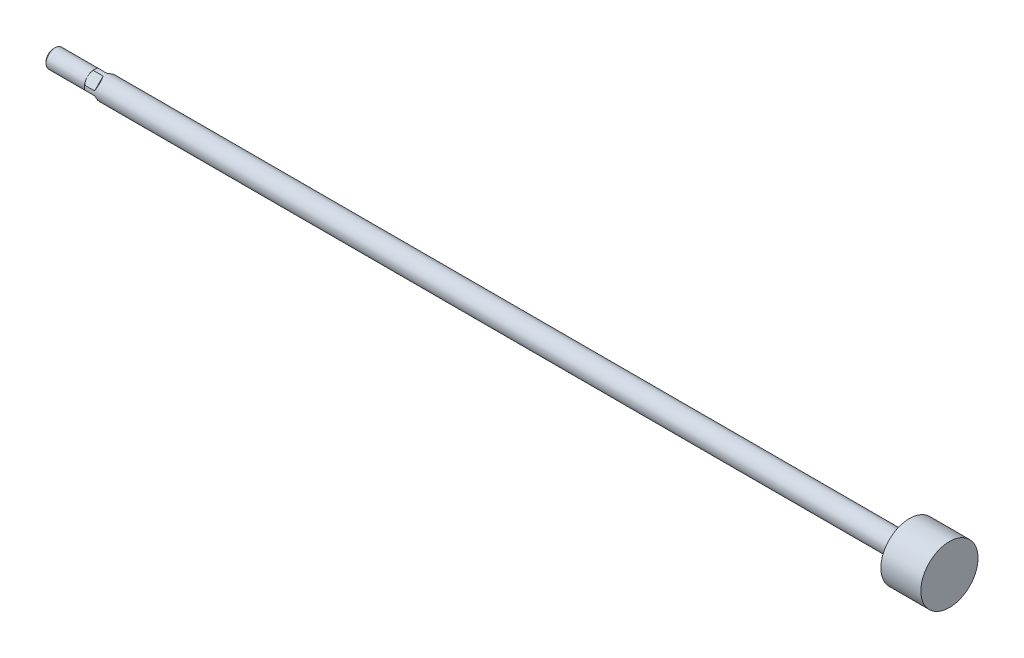
SolidWorks part; units mm, degrees
ref_plane "前视基准面" through (0, 0, 0) normal (0, 0, 1) x (1, 0, 0)
ref_plane "上视基准面" through (0, 0, 0) normal (0, 1, 0) x (1, 0, 0)
ref_plane "右视基准面" through (0, 0, 0) normal (1, 0, 0) x (0, 0, -1)
sketch "草图1" plane through (0, 0, 0) normal (0, 0, 1) x (1, 0, 0)
  line L0 (0, 0) -> (0, 4.233)
  line L1 (0, 4.233) -> (0.767, 5)
  line L2 (0.767, 5) -> (22, 5)
  line L3 (22, 5) -> (23, 6)
  line L4 (23, 6) -> (471, 6)
  line L5 (471, 6) -> (471, 15.75)
  line L6 (471, 15.75) -> (493, 15.75)
  line L7 (493, 15.75) -> (493, 0)
  line L8 (493, 0) -> (0, 0)
  line L9 (493, 0) -> (0, 0) construction
revolve "旋转1" add sketch "草图1" angle 360 about L9 reverse direction yes
cosmetic thread "装饰螺纹线1" parameters "D1"=22, "D2"=8.466
ref_plane "基准面4" through (30, 0, 0) normal (1, 0, 0) x (0, 0, -1)
ref_plane "基准面5" through (11, 0, 0) normal (1, 0, 0) x (0, 0, -1)
ref_plane "基准面6" through (0, 0, 0) normal (0, -0.7071, 0.7071) x (1, 0, 0)
sketch "草图2" plane through (0, 0, 0) normal (0, -0.7071, 0.7071) x (1, 0, 0)
  line L0 (-5, -12) -> (35.4, -12)
  line L1 (35.4, -12) -> (28.4, -5)
  line L2 (28.4, -5) -> (22, -5)
  line L3 (22, -5) -> (19.8, -7.2)
  line L4 (19.8, -7.2) -> (19.8, -10)
  line L5 (19.8, -10) -> (-3, -10)
  line L6 (-3, -10) -> (-3, 10)
  line L7 (-3, 10) -> (19.8, 10)
  line L8 (19.8, 10) -> (19.8, 7.2)
  line L9 (19.8, 7.2) -> (22, 5)
  line L10 (22, 5) -> (28.4, 5)
  line L11 (28.4, 5) -> (35.4, 12)
  line L12 (35.4, 12) -> (-5, 12)
  line L13 (-5, 12) -> (-5, -12)
extrude "切除-拉伸1" cut sketch "草图2" along normal blind 5 and the other way blind 5
ref_plane "基准面7" through (0, 0, 0) normal (0, -0.7071, -0.7071) x (-1, 0, 0)
sketch "草图3" plane through (0, 0, 0) normal (0, -0.7071, -0.7071) x (-1, 0, 0)
  line L0 (5, 12) -> (-35.4, 12)
  line L1 (-35.4, 12) -> (-28.4, 5)
  line L2 (-28.4, 5) -> (-22, 5)
  line L3 (-22, 5) -> (-19.8, 7.2)
  line L4 (-19.8, 7.2) -> (-19.8, 10)
  line L5 (-19.8, 10) -> (3, 10)
  line L6 (3, 10) -> (3, -10)
  line L7 (3, -10) -> (-19.8, -10)
  line L8 (-19.8, -10) -> (-19.8, -7.2)
  line L9 (-19.8, -7.2) -> (-22, -5)
  line L10 (-22, -5) -> (-28.4, -5)
  line L11 (-28.4, -5) -> (-35.4, -12)
  line L12 (-35.4, -12) -> (5, -12)
  line L13 (5, -12) -> (5, 12)
extrude "切除-拉伸2" cut sketch "草图3" along normal blind 5 and the other way blind 5
ref_plane "nut-rod XY" through (11, 0, 0) normal (-1, 0, 0) x (0, 0, 1)
ref_plane "nut-rod XZ" through (0, 0, 0) normal (0, 1, 0) x (1, 0, 0)
ref_plane "nut-rod YZ" through (0, 0, 0) normal (0, 0, -1) x (-1, 0, 0)
ref_axis "nut-rod X" through (11, 0, 80.9) along (0, 0, -1)
ref_axis "nut-rod Y" through (11, 50, 0) along (0, -1, 0)
ref_axis "nut-rod Z" through (-80.9, 0, 0) along (1, 0, 0)
sketch3d "nut-rod"
  point P0 (11, 0, 0)
ref_plane "rod XY" through (30, 0, 0) normal (-1, 0, 0) x (0, 0, 1)
ref_plane "rod XZ" through (0, 0, 0) normal (0, 1, 0) x (1, 0, 0)
ref_plane "rod YZ" through (0, 0, 0) normal (0, 0, -1) x (-1, 0, 0)
ref_axis "rod X" through (30, 0, 80.9) along (0, 0, -1)
ref_axis "rod Y" through (30, 50, 0) along (0, -1, 0)
ref_axis "rod Z" through (-80.9, 0, 0) along (1, 0, 0)
sketch3d "rod"
  point P0 (30, 0, 0)
